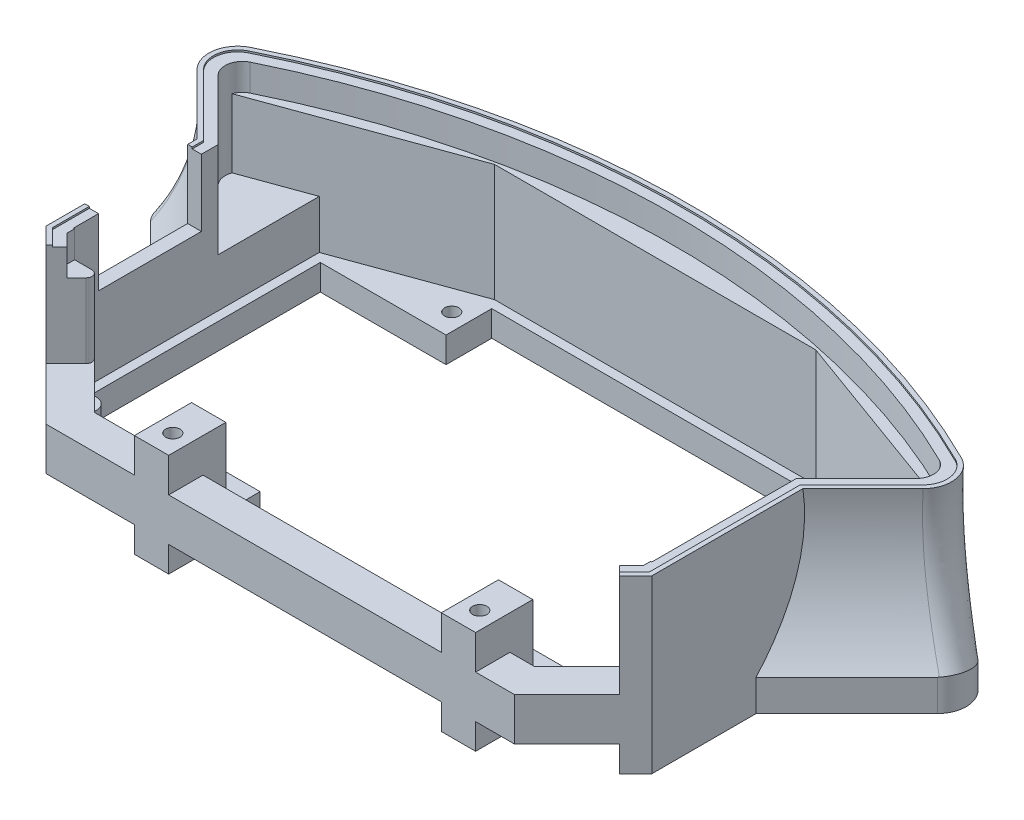
SolidWorks part; units mm, degrees
material "ABS"
ref_plane "Front Plane" through (0, 0, 0) normal (0, 0, 1) x (1, 0, 0)
ref_plane "Top Plane" through (0, 0, 0) normal (0, 1, 0) x (1, 0, 0)
ref_plane "Right Plane" through (0, 0, 0) normal (1, 0, 0) x (0, 0, -1)
sketch "Sketch1" plane through (0, 0, 0) normal (0, 1, 0) x (1, 0, 0)
  line L0 (53, 80) -> (53, 129.1478)
  line L1 (-53, 129.1478) -> (-53, 80)
  line L2 (-41, 68) -> (41, 68)
  line L3 (-53, 80) -> (-41, 68)
  line L4 (41, 68) -> (53, 80)
  circle A0 centre (0, 0) radius 140 construction
  arc A1 (53, 129.1478) -> (-53, 129.1478) centre (0, 0) ccw
  dimension "D1" = 280
  dimension "D3" = 139.6
  dimension "D2" = 106
  dimension "D4" = 68
  dimension "D5" = 80
  dimension "D6" = 135
  dimension "D7" = 135
extrude "Boss-Extrude1" add sketch "Sketch1" along normal blind 30
sketch "Sketch2" plane through (0, 30, 0) normal (0, 1, 0) x (1, 0, 0)
  line L0 (-49, 84) -> (49, 84)
  line L1 (49, 84) -> (49, 124)
  line L2 (49, 124) -> (27, 124)
  line L3 (27, 124) -> (27, 132)
  line L4 (27, 132) -> (-27, 132)
  line L5 (-27, 132) -> (-27, 124)
  line L6 (-27, 124) -> (-49, 124)
  line L7 (-49, 124) -> (-49, 84)
  line L12 (-53, 129.1478) -> (-53, 80) construction
  dimension "D1" = 48
  dimension "D2" = 98
  dimension "D3" = 8
  dimension "D4" = 84
  dimension "D5" = 22
  dimension "D6" = 4
extrude "Cut-Extrude1" cut sketch "Sketch2" against normal up to next
sketch "Sketch3" plane through (0, 30, 0) normal (0, 1, 0) x (1, 0, 0)
  line L0 (-50, 83) -> (50, 83) construction
  line L1 (50, 83) -> (50, 125) construction
  line L2 (50, 125) -> (28, 133) construction
  line L3 (28, 133) -> (-28, 133) construction
  line L4 (-28, 133) -> (-50, 125) construction
  line L5 (-50, 125) -> (-50, 83) construction
  line L7 (-49, 84) -> (-49, 124) construction
  line L8 (-50.6, 125.4203) -> (-50.6, 82.4)
  line L9 (-50.6, 82.4) -> (50.6, 82.4)
  line L10 (50.6, 82.4) -> (50.6, 125.4203)
  line L11 (50.6, 125.4203) -> (28.1057, 133.6)
  line L12 (28.1057, 133.6) -> (-28.1057, 133.6)
  line L13 (-28.1057, 133.6) -> (-50.6, 125.4203)
  line L16 (-49, 84) -> (49, 84) construction
  dimension "D1" = 50
  dimension "D2" = 22
  dimension "D3" = 8
  dimension "D4" = 1
  dimension "D5" = 1
  dimension "D6" = 100
  dimension "D7" = 0.6
extrude "Cut-Extrude2" cut sketch "Sketch3" against normal offset from surface (25.5 mm away) 4.5 up to face at (0, 0, -116)
sketch "Sketch5" plane through (0, 30, 0) normal (0, 1, 0) x (1, 0, 0)
  line L1 (-37.48, 68.91) -> (43.8, 68.91) construction
  line L2 (-37.48, 68.91) -> (-37.48, 122.25) construction
  line L3 (-37.48, 122.25) -> (43.8, 122.25) construction
  line L4 (43.8, 68.91) -> (43.8, 122.25) construction
  line L6 (-37.88, 68.51) -> (-37.88, 122.65)
  line L7 (-37.88, 122.65) -> (44.2, 122.65)
  line L8 (44.2, 68.51) -> (44.2, 122.65)
  line L9 (-37.88, 68.51) -> (44.2, 68.51)
  dimension "D1" = 68.91
  dimension "D2" = 43.8
  dimension "D3" = 81.28
  dimension "D4" = 53.34
  dimension "D5" = 0.4
extrude "Cut-Extrude4" cut sketch "Sketch5" against normal offset from surface (12 mm away) 18 up to face at (0, 0, -116)
sketch "Sketch4" plane through (0, 18, 0) normal (0, 1, 0) x (1, 0, 0)
  circle A0 centre (31.18, 71.72) radius 1.25
  circle A1 centre (-22.53, 71.72) radius 1.25
  dimension "D2" = 2.5
  dimension "D1" = 22.53
  dimension "D3" = 8.28
  dimension "D4" = 53.71
extrude "Cut-Extrude3" cut sketch "Sketch4" against normal up to next
sketch "Sketch6" plane through (0, 30, 0) normal (0, 1, 0) x (1, 0, 0)
  line L5 (53, 80) -> (53, 129.1478) construction
  line L6 (-53, 129.1478) -> (-53, 80) construction
  line L7 (-41, 68) -> (41, 68) construction
  line L8 (-53, 80) -> (-41, 68) construction
  line L9 (44.2, 71.2) -> (53, 80) construction
  line L25 (50.4, 81.077) -> (50.4, 127.3925)
  line L26 (39.923, 70.6) -> (50.4, 81.077)
  line L27 (-39.923, 70.6) -> (39.923, 70.6)
  line L28 (-50.4, 81.077) -> (-39.923, 70.6)
  line L29 (-50.4, 127.3925) -> (-50.4, 81.077)
  arc A1 (53, 129.1478) -> (-53, 129.1478) centre (0, 0) ccw construction
  arc A8 (50.4, 127.3925) -> (-50.4, 127.3925) centre (0, 0) ccw
  dimension "D3" = 2.6
  dimension "D1" = 2.6
  dimension "D2" = 2.6
  dimension "D4" = 2.6
  dimension "D5" = 2.6
  dimension "D6" = 2.6
extrude "Cut-Extrude5" cut sketch "Sketch6" against normal blind 5
sketch "Sketch7" plane through (0, 0, 0) normal (0, -1, 0) x (1, 0, 0)
  line L0 (73.4563, -118.7111) -> (53, -98.2548)
  line L1 (53, -80) -> (53, -129.1478) construction
  line L2 (53, -98.2548) -> (53, -129.1478)
  line L3 (0, 0) -> (103.3995, -103.3995) construction
  arc A0 (53, -129.1478) -> (73.4563, -118.7111) centre (0, 0) ccw
  arc A1 (-53, -129.1478) -> (53, -129.1478) centre (0, 0) ccw construction
  dimension "D1" = 45
  dimension "D2" = 32
extrude "Boss-Extrude2" add sketch "Sketch7" against normal up to surface (30 mm away) up to face at (0.5928, 30, -93.6257)
ref_plane "Plane1" through (96.0837, 0, -96.0837) normal (-0.7071, 0, 0.7071) x (0, -1, 0)
sketch "Sketch8" plane through (96.0837, 0, -96.0837) normal (-0.7071, 0, 0.7071) x (0, -1, 0)
  line L0 (-30, -32) -> (0, -32) construction
  circle A0 centre (-26, 0) radius 38
  dimension "D3" = 76
  dimension "D1" = 32
  dimension "D2" = 26
extrude "Cut-Extrude6" cut sketch "Sketch8" along normal up to surface (98.9296 mm away) up to face at (53, 18.75, -84.5637)
mirror "Mirror1" about plane through (0, 0, 0) normal (1, 0, 0) of "Boss-Extrude2"
ref_plane "Plane2" through (-96.0837, 0, -96.0837) normal (0.7071, 0, 0.7071) x (0, -1, 0)
sketch "Sketch9" plane through (-96.0837, 0, -96.0837) normal (0.7071, 0, 0.7071) x (0, -1, 0)
  line L0 (-30, 32) -> (0, 32) construction
  circle A0 centre (-26, 0) radius 38
  dimension "D1" = 76
  dimension "D2" = 32
  dimension "D3" = 26
extrude "Cut-Extrude7" cut sketch "Sketch9" along normal up to surface (22.9296 mm away) up to face at (-53, 18.75, -93.6911)
fillet "Fillet2" radius 5 4 edges at (69.0949, 16.9868, -121.3015) (73.4563, 2.753, -118.7111) (-73.4563, 2.753, -118.7111) (-68.9598, 17.6248, -121.3784)
sketch "Sketch11" plane through (0, 4.5, 0) normal (0, 1, 0) x (1, 0, 0)
  line L0 (-49, 124) -> (-27, 124) construction
  circle A0 centre (-30, 128) radius 1.25
  circle A1 centre (30, 128) radius 1.25
  dimension "D2" = 2.5
  dimension "D1" = 4
  dimension "D3" = 60
  dimension "D4" = 30
extrude "Cut-Extrude9" cut sketch "Sketch11" against normal up to next
sketch "Sketch12" plane through (0, 30, 0) normal (0, 1, 0) x (1, 0, 0)
  line L0 (-61.0884, 118.2069) -> (-50.4, 107.5185)
  line L2 (-50.4, 107.5185) -> (-50.4, 127.3925)
  line L3 (-63.5251, 116.9667) -> (-53, 106.4416) construction
  arc A0 (-50.4, 127.3925) -> (-60.2872, 123.0221) centre (0, 0) ccw
  arc A1 (-60.2872, 123.0221) -> (-61.0884, 118.2069) centre (-58.9671, 120.3282) ccw
  arc A3 (62.1871, 124.9837) -> (-62.1871, 124.9837) centre (0, 0) ccw construction
  dimension "D1" = 2.6
  dimension "D2" = 3
extrude "Cut-Extrude10" cut sketch "Sketch12" against normal offset from surface (17 mm away) 5 up to face at (-22.53, 18, -70.47) offset beyond the face yes
sketch "Sketch14" plane through (0, 13, 0) normal (0, 1, 0) x (1, 0, 0)
  line L0 (-50.4, 127.3925) -> (-61.7869, 123.2518)
  line L1 (-61.7869, 123.2518) -> (-61.7869, 121.3523)
  line L2 (-61.7869, 121.3523) -> (-50.4, 125.493)
  line L3 (-50.4, 125.493) -> (-50.4, 127.3925)
  line L4 (-50.6, 125.4203) -> (-28.1057, 133.6) construction
  arc A0 (-60.2872, 123.0221) -> (-61.0884, 118.2069) centre (-58.9671, 120.3282) ccw construction
extrude "Boss-Extrude3" add sketch "Sketch14" along normal up to surface (12 mm away) up to face at (0, 25, -130.4297)
mirror "Mirror2" about plane through (0, 0, 0) normal (1, 0, 0) of "Boss-Extrude3", "Cut-Extrude10"
sketch "Sketch15" plane through (0, 30, 0) normal (0, 1, 0) x (1, 0, 0)
  line L0 (-50.1716, 77.1716) -> (-43.3431, 84)
  line L1 (-53, 80) -> (-41, 68) construction
  line L2 (49, 84) -> (-49, 84) construction
  line L3 (-43.3431, 84) -> (43.3431, 84)
  line L4 (43.3431, 84) -> (50.1716, 77.1716)
  line L5 (41, 68) -> (41.51, 68.51) construction
  line L6 (50.1716, 77.1716) -> (41, 68)
  line L7 (41, 68) -> (-41, 68)
  line L8 (-41, 68) -> (-50.1716, 77.1716)
  dimension "D1" = 4
  dimension "D2" = 4
extrude "Cut-Extrude12" cut sketch "Sketch15" against normal up to surface (12 mm away) up to face at (-22.53, 18, -70.47)
sketch "Sketch16" plane through (0, 18, 0) normal (0, 1, 0) x (1, 0, 0)
  line L0 (-50.1716, 77.1716) -> (-44.9431, 82.4)
  line L1 (-44.9431, 82.4) -> (-25.53, 82.4)
  line L2 (50.6, 82.4) -> (-50.6, 82.4) construction
  line L3 (-25.53, 82.4) -> (-25.53, 68)
  line L4 (41, 68) -> (-41, 68) construction
  line L5 (-25.53, 68) -> (-41, 68)
  line L6 (-41, 68) -> (-50.1716, 77.1716) construction
  line L7 (-41, 68) -> (-50.1716, 77.1716)
  line L8 (44.9431, 82.4) -> (-44.9431, 82.4) construction
  line L9 (-19.53, 68) -> (28.18, 68)
  line L10 (-19.53, 68) -> (-19.53, 82.4)
  line L11 (-19.53, 82.4) -> (28.18, 82.4)
  line L12 (28.18, 68) -> (28.18, 82.4)
  line L13 (34.18, 82.4) -> (34.18, 68)
  line L14 (34.18, 68) -> (41, 68)
  line L15 (41, 68) -> (50.1716, 77.1716)
  line L16 (50.1716, 77.1716) -> (44.9431, 82.4)
  line L17 (44.9431, 82.4) -> (34.18, 82.4)
  circle A0 centre (31.18, 71.72) radius 1.25 construction
  circle A3 centre (-22.53, 71.72) radius 1.25 construction
  dimension "D1" = 3
  dimension "D2" = 3
  dimension "D3" = 3
  dimension "D4" = 3
extrude "Cut-Extrude13" cut sketch "Sketch16" against normal blind 6
sketch "Sketch20" plane through (0, 0, 0) normal (0, -1, 0) x (1, 0, 0)
  line L0 (-50.1716, -77.1716) -> (-41, -68)
  line L1 (-41, -68) -> (-25.53, -68)
  line L2 (-25.53, -68) -> (-25.53, -84)
  line L3 (-25.53, -84) -> (-43.3431, -84)
  line L4 (-43.3431, -84) -> (-50.1716, -77.1716)
  line L5 (-19.53, -84) -> (28.18, -84)
  line L6 (-19.53, -84) -> (-19.53, -68)
  line L7 (-19.53, -68) -> (28.18, -68)
  line L8 (28.18, -84) -> (28.18, -68)
  line L9 (34.18, -68) -> (34.18, -84)
  line L10 (34.18, -84) -> (43.3431, -84)
  line L11 (43.3431, -84) -> (50.1716, -77.1716)
  line L12 (50.1716, -77.1716) -> (41, -68)
  line L13 (41, -68) -> (34.18, -68)
  line L14 (-41, -68) -> (41, -68) construction
  line L15 (41, -68) -> (53, -80) construction
  line L16 (49, -84) -> (-49, -84) construction
  line L17 (-53, -80) -> (-41, -68) construction
extrude "Cut-Extrude17" cut sketch "Sketch20" against normal up to surface (4.5 mm away) up to face at (30, 4.5, -126.75)
fillet "Fillet4" radius 2 2 edges at (43.3431, 2.25, -84) (-43.3431, 2.25, -84)
sketch "Sketch17" plane through (0, 0, 0) normal (0, -1, 0) x (1, 0, 0)
  circle A0 centre (-55, -115) radius 1.25
  circle A1 centre (55, -115) radius 1.25
  dimension "D1" = 2.5
  dimension "D2" = 115
  dimension "D3" = 55
  dimension "D4" = 55
extrude "Cut-Extrude14" cut sketch "Sketch17" against normal blind 12
fillet "Fillet3" radius 1 2 edges at (44.9431, 18.5, -82.4) (-44.9431, 18.5, -82.4)
sketch "Sketch18" plane through (0, 18, 0) normal (0, 1, 0) x (1, 0, 0)
  line L0 (34.18, 82.4) -> (34.18, 68) construction
  line L1 (-25.53, 82.4) -> (34.18, 82.4)
  line L2 (-25.53, 82.4) -> (-25.53, 78)
  line L3 (-25.53, 78) -> (34.18, 78)
  line L4 (34.18, 82.4) -> (34.18, 78)
  line L5 (-19.53, 68) -> (-25.53, 68) construction
  dimension "D1" = 10
extrude "Cut-Extrude15" cut sketch "Sketch18" against normal up to surface (6 mm away) up to face at (-39.2781, 12, -76.4835)
sketch "Sketch19" plane through (0, 30, 0) normal (0, 1, 0) x (1, 0, 0)
  line L0 (-53, 106.7401) -> (-53, 98.2548) construction
  line L1 (-53, 104.7916) -> (-49, 104.7916)
  line L2 (-53, 104.7916) -> (-53, 86.7916)
  line L3 (-53, 86.7916) -> (-49, 86.7916)
  line L4 (-49, 104.7916) -> (-49, 86.7916)
  line L6 (-49, 84) -> (-49, 124) construction
  circle A0 centre (-22.53, 71.72) radius 1.25 construction
  dimension "D1" = 15.0716
  dimension "D2" = 18
extrude "Cut-Extrude16" cut sketch "Sketch19" against normal up to surface (12 mm away) up to face at (-22.53, 18, -73)
sketch "Sketch21" plane through (0, 30, 0) normal (0, 1, 0) x (1, 0, 0)
  line L19 (-52.2, 106.7729) -> (-52.2, 80.3314)
  line L20 (-52.2, 80.3314) -> (-49.6059, 77.7373)
  line L21 (-46.6503, 80.6929) -> (-50.1716, 77.1716) construction
  line L22 (-49.6059, 77.7373) -> (49.6059, 77.7373)
  line L23 (-52.2, 106.7729) -> (-52.2, 104.7916)
  line L24 (-62.9594, 117.5324) -> (-52.2, 106.7729)
  line L25 (52.2, 80) -> (52.2, 106.7729)
  line L26 (52.2, 106.7729) -> (62.9594, 117.5324)
  line L27 (50.1716, 77.1716) -> (46.6503, 80.6929) construction
  line L28 (-62.9594, 117.5324) -> (-52.2, 106.7729)
  line L29 (52.2, 80.3314) -> (52.2, 106.7729)
  line L30 (52.2, 106.7729) -> (62.9594, 117.5324)
  line L31 (49.6059, 77.7373) -> (52.2, 80.3314)
  line L33 (50.1716, 77.1716) -> (48.3331, 79.0101) construction
  line L34 (50.1716, 77.1716) -> (53, 80) construction
  line L35 (-53, 80) -> (-50.1716, 77.1716) construction
  arc A10 (61.8307, 124.2675) -> (-61.8307, 124.2675) centre (0, 0) ccw
  arc A11 (61.8307, 124.2675) -> (-61.8307, 124.2675) centre (0, 0) ccw
  spline S17 degree 3 poles (-2791.6803, -793.6282) (-151.1922, 208.4655) (47.8929, 98.3145) (63.3918, 118.0343) (63.4863, 118.1707) (63.7432, 118.5921) (63.884, 118.9004) (64.0846, 119.5295) (64.1477, 119.857) (64.1947, 120.5225) (64.1784, 120.8524) (64.0962, 121.3423) (64.0584, 121.5068) (63.9649, 121.8259) (63.9091, 121.9814) (63.7145, 122.4378) (63.5472, 122.7299) (63.1503, 123.2644) (62.9241, 123.5045) (41.0501, 141.8435) (-151.6347, -61.6595) (1792.5456, -2310.831) knots -9.381466 -9.381466 -9.381466 -9.381466 0.0625 0.0625 0.125 0.125 0.25 0.25 0.375 0.375 0.5 0.5 0.5625 0.5625 0.625 0.625 0.75 0.75 0.875 0.875 11.418904 11.418904 11.418904 11.418904 only from (62.9594, 117.5324) to (61.8307, 124.2675)
  spline S18 degree 3 poles (2933.466, 32.8068) (113.3304, -31.1396) (-41.1568, 137.8252) (-62.4023, 123.9288) (-62.5359, 123.8296) (-62.9156, 123.5123) (-63.1493, 123.2653) (-63.5445, 122.7339) (-63.711, 122.4452) (-63.974, 121.8299) (-64.0669, 121.5128) (-64.15, 121.0237) (-64.1683, 120.8561) (-64.1847, 120.5237) (-64.1829, 120.3586) (-64.16, 120.0292) (-64.1388, 119.8649) (-64.0769, 119.5398) (-64.0357, 119.3767) (-63.8846, 118.9013) (-63.7481, 118.6013) (-63.4897, 118.1756) (-63.394, 118.0374) (-47.2585, 97.4867) (150.4821, 235.4732) (2678.3171, -1087.2581) knots -9.468277 -9.468277 -9.468277 -9.468277 0.0625 0.0625 0.125 0.125 0.25 0.25 0.375 0.375 0.5 0.5 0.5625 0.5625 0.625 0.625 0.6875 0.6875 0.75 0.75 0.875 0.875 0.9375 0.9375 10.676928 10.676928 10.676928 10.676928 only from (-61.8307, 124.2675) to (-62.9594, 117.5324)
  spline S19 degree 3 poles (62.9594, 117.5324) (63.0781, 117.651) (63.188, 117.775) (63.3918, 118.0343) (63.4863, 118.1707) (63.7432, 118.5921) (63.884, 118.9004) (64.0846, 119.5295) (64.1477, 119.857) (64.1947, 120.5225) (64.1784, 120.8524) (64.0962, 121.3423) (64.0584, 121.5068) (63.9649, 121.8259) (63.9091, 121.9814) (63.7145, 122.4378) (63.5472, 122.7299) (63.1503, 123.2644) (62.9241, 123.5045) (62.4115, 123.9342) (62.1312, 124.118) (61.8307, 124.2675) knots 0 0 0 0 0.0625 0.0625 0.125 0.125 0.25 0.25 0.375 0.375 0.5 0.5 0.5625 0.5625 0.625 0.625 0.75 0.75 0.875 0.875 1 1 1 1
  spline S20 degree 3 poles (-61.8307, 124.2675) (-61.9813, 124.1925) (-62.1254, 124.1099) (-62.4023, 123.9288) (-62.5359, 123.8296) (-62.9156, 123.5123) (-63.1493, 123.2653) (-63.5445, 122.7339) (-63.711, 122.4452) (-63.974, 121.8299) (-64.0669, 121.5128) (-64.15, 121.0237) (-64.1683, 120.8561) (-64.1847, 120.5237) (-64.1829, 120.3586) (-64.16, 120.0292) (-64.1388, 119.8649) (-64.0769, 119.5398) (-64.0357, 119.3767) (-63.8846, 118.9013) (-63.7481, 118.6013) (-63.4897, 118.1756) (-63.394, 118.0374) (-63.1882, 117.7753) (-63.0779, 117.6508) (-62.9594, 117.5324) knots 0 0 0 0 0.0625 0.0625 0.125 0.125 0.25 0.25 0.375 0.375 0.5 0.5 0.5625 0.5625 0.625 0.625 0.6875 0.6875 0.75 0.75 0.875 0.875 0.9375 0.9375 1 1 1 1
  dimension "D2" = 0.8
  dimension "D1" = 0.8
extrude "Cut-Extrude18" cut sketch "Sketch21" against normal blind 0.3
sketch "Sketch22" plane through (0, 12, 0) normal (0, 1, 0) x (1, 0, 0)
  line L0 (-46.9147, 82.4) -> (-38.5147, 74)
  line L1 (47.3574, 82.4) -> (-47.3574, 82.4) construction
  line L2 (-38.5147, 74) -> (-25.53, 74)
  line L3 (-25.53, 68) -> (-25.53, 78) construction
  line L4 (-25.53, 74) -> (-25.53, 78)
  line L5 (-25.53, 78) -> (-19.53, 78)
  line L6 (-19.53, 78) -> (-19.53, 74)
  line L7 (-19.53, 78) -> (-19.53, 68) construction
  line L8 (-19.53, 74) -> (28.18, 74)
  line L9 (28.18, 68) -> (28.18, 78) construction
  line L10 (28.18, 74) -> (28.18, 78)
  line L11 (28.18, 78) -> (34.18, 78)
  line L12 (34.18, 78) -> (34.18, 74)
  line L13 (34.18, 78) -> (34.18, 68) construction
  line L14 (34.18, 74) -> (38.5147, 74)
  line L15 (38.5147, 74) -> (46.9147, 82.4)
  line L16 (46.9147, 82.4) -> (-46.9147, 82.4)
  line L17 (-41, 68) -> (-25.53, 68) construction
  line L19 (-50.1716, 77.1716) -> (-41, 68) construction
  line L20 (41, 68) -> (50.1716, 77.1716) construction
  dimension "D1" = 6
  dimension "D2" = 6
  dimension "D3" = 6
extrude "Cut-Extrude19" cut sketch "Sketch22" against normal up to surface (7.5 mm away) up to face at (-22.53, 4.5, -83.2)
